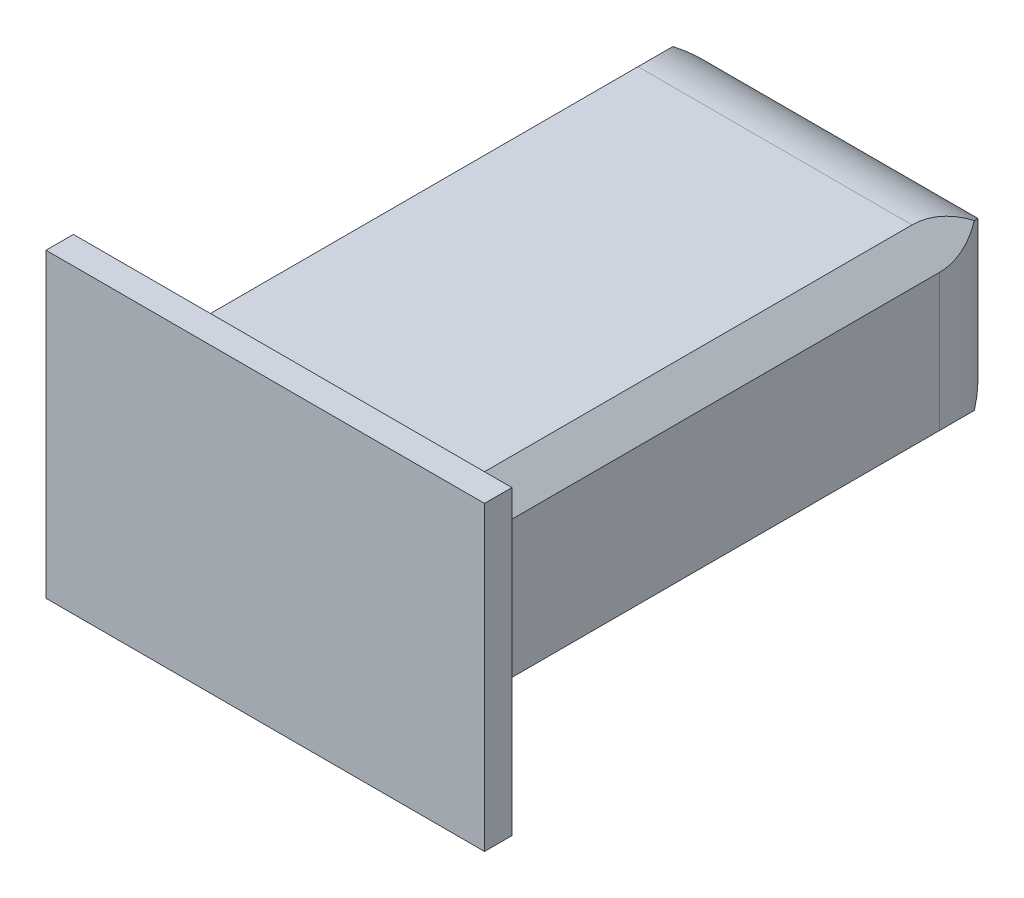
SolidWorks part; units mm, degrees
ref_plane "Front Plane" through (0, 0, 0) normal (0, 0, 1) x (1, 0, 0)
ref_plane "Top Plane" through (0, 0, 0) normal (0, 1, 0) x (1, 0, 0)
ref_plane "Right Plane" through (0, 0, 0) normal (1, 0, 0) x (0, 0, -1)
sketch "Sketch1" plane through (0, 0, 0) normal (0, 0, 1) x (1, 0, 0)
  line L1 (-1.5, 0.875) -> (1.5, 0.875)
  line L2 (-1.5, 0.875) -> (-1.5, -0.875)
  line L3 (-1.5, -0.875) -> (1.5, -0.875)
  line L4 (1.5, 0.875) -> (1.5, -0.875)
  line L5 (-1.5, 0.875) -> (1.5, -0.875) construction
  line L6 (-1.5, -0.875) -> (1.5, 0.875) construction
  point P0 (0, 0)
  dimension "D1" = 3
  dimension "D2" = 1.75
extrude "Boss-Extrude1" add sketch "Sketch1" along normal blind 5
sketch "Sketch2" plane through (0, 0, 5) normal (0, 0, 1) x (1, 0, 0)
  line L4 (2, 1.375) -> (-2, 1.375)
  line L5 (-2, 1.375) -> (-2, -1.375)
  line L6 (-2, -1.375) -> (2, -1.375)
  line L7 (2, -1.375) -> (2, 1.375)
  line L8 (1.5, -0.875) -> (1.5, 0.875)
  line L9 (1.5, 0.875) -> (-1.5, 0.875)
  line L10 (-1.5, 0.875) -> (-1.5, -0.875)
  line L11 (-1.5, -0.875) -> (1.5, -0.875)
  line L12 (1.5, -0.875) -> (1.5, 0.875)
  line L13 (1.5, 0.875) -> (-1.5, 0.875)
  line L14 (-1.5, 0.875) -> (-1.5, -0.875)
  line L15 (-1.5, -0.875) -> (1.5, -0.875)
  line M5 (1.5, -0.875) -> (1.5, 0.875)
  line M6 (1.5, 0.875) -> (-1.5, 0.875)
  line M7 (-1.5, 0.875) -> (-1.5, -0.875)
  line M8 (-1.5, -0.875) -> (1.5, -0.875)
  dimension "D1" = 0
  dimension "D2" = 0.5
extrude "Boss-Extrude2" add sketch "Sketch2" along normal blind 0.5 contours M8 M5 M6 M7 | L6 L7 L4 L5 M5 M8 M7 M6 region at (1.9515, 0, 5) region at (0, 0, 5)
chamfer "Chamfer1" distance 0.25 angle 45 8 edges at (-2, 0, 5) (0, -1.375, 5) (2, 0, 5) (0, 1.375, 5) (-1.5, 0.875, 2.5) (-1.5, -0.875, 2.5) (1.5, -0.875, 2.5) (1.5, 0.875, 2.5)
fillet "Fillet1" radius 0.85 4 edges at (0, 0.875, 0) (-1.5, 0, 0) (0, -0.875, 0) (1.5, 0, 0)
